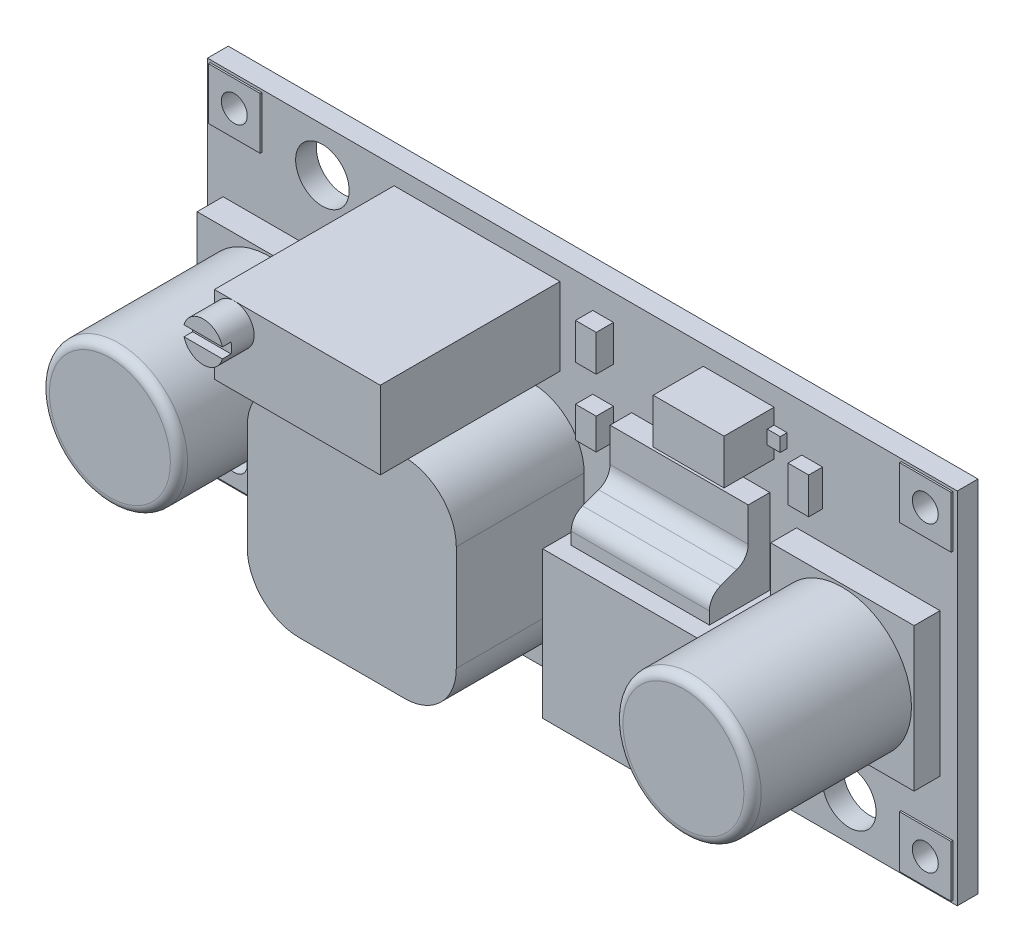
SolidWorks part; units mm, degrees
ref_plane "Přední rovina" through (0, 0, 0) normal (0, 0, 1) x (1, 0, 0)
ref_plane "Horní rovina" through (0, 0, 0) normal (0, 1, 0) x (1, 0, 0)
ref_plane "Pravá rovina" through (0, 0, 0) normal (1, 0, 0) x (0, 0, -1)
sketch "Skica1" plane through (0, 0, 0) normal (0, 0, 1) x (1, 0, 0)
  line L1 (-21.7, -10.4) -> (21.7, -10.4)
  line L2 (-21.7, -10.4) -> (-21.7, 10.4)
  line L3 (-21.7, 10.4) -> (21.7, 10.4)
  line L4 (21.7, -10.4) -> (21.7, 10.4)
  line L5 (-21.7, -10.4) -> (21.7, 10.4) construction
  line L6 (-21.7, 10.4) -> (21.7, -10.4) construction
  circle A0 centre (-15.05, 7.85) radius 1.55
  circle A1 centre (15.45, -8.05) radius 1.55
  point P0 (0, 0)
  dimension "D3" = 3.1
  dimension "D4" = 1
  dimension "D5" = 0.8
  dimension "D6" = 5.1
  dimension "D7" = 4.7
  dimension "D1" = 43.4
  dimension "D2" = 20.8
extrude "Přidat vysunutím1" add sketch "Skica1" along normal blind 1.2
sketch "Skica3" plane through (0, 0, 1.2) normal (0, 0, 1) x (1, 0, 0)
  line L0 (-21.7, -10.4) -> (21.7, -10.4) construction
  line L1 (-12, -8.6) -> (0.1, -8.6)
  line L2 (-12, -8.6) -> (-12, 3.5)
  line L3 (-12, 3.5) -> (0.1, 3.5)
  line L4 (0.1, -8.6) -> (0.1, 3.5)
  line L5 (-12, -8.6) -> (0.1, 3.5) construction
  line L6 (-12, 3.5) -> (0.1, -8.6) construction
  line L7 (-21.7, 10.4) -> (-21.7, -10.4) construction
  point P0 (-5.95, -2.55)
  dimension "D1" = 12.1
  dimension "D2" = 1.8
  dimension "D3" = 9.7
extrude "Přidat vysunutím2" add sketch "Skica3" along normal blind 7.4
fillet "Zaoblit1" radius 3 4 edges at (-12, -8.6, 4.9) (-12, 3.5, 4.9) (0.1, 3.5, 4.9) (0.1, -8.6, 4.9)
sketch "Skica4" plane through (0, 0, 1.2) normal (0, 0, 1) x (1, 0, 0)
  line L0 (21.7, 10.4) -> (-21.7, 10.4) construction
  line L1 (-1.3, 4.9) -> (-10.9, 4.9)
  line L2 (-1.3, 4.9) -> (-1.3, 9.4)
  line L3 (-1.3, 9.4) -> (-10.9, 9.4)
  line L4 (-10.9, 4.9) -> (-10.9, 9.4)
  line L5 (-1.3, 4.9) -> (-10.9, 9.4) construction
  line L6 (-1.3, 9.4) -> (-10.9, 4.9) construction
  line L7 (-21.7, 10.4) -> (-21.7, -10.4) construction
  point P0 (-6.1, 7.15)
  dimension "D1" = 4.5
  dimension "D2" = 9.6
  dimension "D3" = 1
  dimension "D4" = 10.8
extrude "Přidat vysunutím3" add sketch "Skica4" along normal blind 10.4
sketch "Skica5" plane through (0, 0, 11.6) normal (0, 0, 1) x (1, 0, 0)
  line L0 (-1.3, 9.4) -> (-10.9, 9.4) construction
  line L1 (-10.9, 9.4) -> (-10.9, 4.9) construction
  circle A0 centre (-9.75, 8.25) radius 1.15
  dimension "D1" = 2.3
extrude "Přidat vysunutím4" add sketch "Skica5" along normal blind 1.8
sketch "Skica6" plane through (0, 0, 1.2) normal (0, 0, 1) x (1, 0, 0)
  line L0 (-21.7, 10.4) -> (-21.7, -10.4) construction
  line L1 (-12.5, -4.4) -> (-20.8, -4.4)
  line L2 (-12.5, -4.4) -> (-12.5, 3.9)
  line L3 (-12.5, 3.9) -> (-20.8, 3.9)
  line L4 (-20.8, -4.4) -> (-20.8, 3.9)
  line L5 (-12.5, -4.4) -> (-20.8, 3.9) construction
  line L6 (-12.5, 3.9) -> (-20.8, -4.4) construction
  line L7 (20.7, -4.4) -> (12.4, -4.4)
  line L8 (20.7, -4.4) -> (20.7, 3.9)
  line L9 (20.7, 3.9) -> (12.4, 3.9)
  line L10 (12.4, -4.4) -> (12.4, 3.9)
  line L11 (20.7, -4.4) -> (12.4, 3.9) construction
  line L12 (20.7, 3.9) -> (12.4, -4.4) construction
  line L13 (21.7, -10.4) -> (21.7, 10.4) construction
  line L14 (21.7, 10.4) -> (-21.7, 10.4) construction
  circle A0 centre (-16.65, -0.25) radius 4
  circle A1 centre (16.55, -0.25) radius 4
  point P0 (-16.65, -0.25)
  point P5 (16.55, -0.25)
  dimension "D4" = 8
  dimension "D1" = 0.9
  dimension "D2" = 1
  dimension "D3" = 6.5
  dimension "D5" = 8.3
extrude "Přidat vysunutím5" add sketch "Skica6" along normal blind 1.5
extrude "Přidat vysunutím6" add sketch "Skica6<2>" along normal blind 10.7 contours A0 | A1 region at (-16.65, -0.25, 1.2) region at (16.55, -0.25, 1.2)
sketch "Skica6<2>" plane through (0, 0, 1.2) normal (0, 0, 1) x (1, 0, 0) same geometry as "Skica6"
fillet "Zaoblit2" radius 0.5 2 edges at (20.55, -0.25, 11.9) (-12.65, -0.25, 11.9)
sketch "Skica7" plane through (0, 0, 1.2) normal (0, 0, 1) x (1, 0, 0)
  line L0 (-21.7, -10.4) -> (21.7, -10.4) construction
  line L1 (2.2, -8.5) -> (11.5, -8.5)
  line L2 (2.2, -8.5) -> (2.2, 0)
  line L3 (2.2, 0) -> (11.5, 0)
  line L4 (11.5, -8.5) -> (11.5, 0)
  line L5 (2.2, -8.5) -> (11.5, 0) construction
  line L6 (2.2, 0) -> (11.5, -8.5) construction
  line L7 (2.2, -9.8) -> (11.5, -9.8)
  line L8 (2.2, -9.8) -> (2.2, 0)
  line L9 (2.2, 0) -> (11.5, 0)
  line L10 (11.5, -9.8) -> (11.5, 0)
  line L11 (2.2, -9.8) -> (11.5, 0) construction
  line L12 (2.2, 0) -> (11.5, -9.8) construction
  line L13 (2.85, 0) -> (10.85, 0)
  line L14 (2.85, 0) -> (2.85, 4.9)
  line L15 (2.85, 4.9) -> (10.85, 4.9)
  line L16 (10.85, 0) -> (10.85, 4.9)
  line L17 (2.85, 0) -> (10.85, 4.9) construction
  line L18 (2.85, 4.9) -> (10.85, 0) construction
  line L19 (2.85, 0) -> (10.85, 0)
  line L20 (2.85, 0) -> (2.85, 1.5)
  line L21 (2.85, 1.5) -> (10.85, 1.5)
  line L22 (10.85, 0) -> (10.85, 1.5)
  line L23 (2.85, 0) -> (10.85, 1.5) construction
  line L24 (2.85, 1.5) -> (10.85, 0) construction
  line L25 (21.7, -10.4) -> (21.7, 10.4) construction
  point P0 (6.85, -4.25)
  point P5 (6.85, -4.9)
  point P10 (6.85, 2.45)
  point P15 (6.85, 0.75)
  dimension "D1" = 8
  dimension "D2" = 9.3
  dimension "D3" = 1.3
  dimension "D4" = 8.5
  dimension "D5" = 10
  dimension "D6" = 13.4
  dimension "D7" = 1.9
  dimension "D8" = 10.2
extrude "Přidat vysunutím7" add sketch "Skica7" along normal blind 4.5 contours L1 L4 L3 L9 L2 region at (6.85, -4.25, 1.2)
extrude "Přidat vysunutím8" add sketch "Skica7<3>" along normal blind 1.4 contours L7 L10 L1 L8 region at (6.85, -9.15, 1.2)
sketch "Skica7<3>" plane through (0, 0, 1.2) normal (0, 0, 1) x (1, 0, 0) same geometry as "Skica7"
extrude "Přidat vysunutím9" add sketch "Skica7<4>" along normal blind 1.25 contours L14 L21 L16 L15 region at (6.85, 3.2, 1.2)
sketch "Skica7<4>" plane through (0, 0, 1.2) normal (0, 0, 1) x (1, 0, 0) same geometry as "Skica7"
extrude "Přidat vysunutím10" add sketch "Skica7<5>" along normal blind 3.5 contours L21 L14 L9 L16 region at (6.85, 0.75, 1.2)
sketch "Skica7<5>" plane through (0, 0, 1.2) normal (0, 0, 1) x (1, 0, 0) same geometry as "Skica7"
chamfer "Zkosení1" distance 2 angle 20 1 edges at (6.85, 1.5, 2.45) first distance on face at (6.85, 1.5, 3.575)
fillet "Zaoblit3" radius 1 1 edges at (6.85, 1.5, 4.7)
fillet "Zaoblit4" radius 1 1 edges at (6.85, 1.5, 4.45)
fillet "Zaoblit5" radius 1 1 edges at (6.85, 2.2279, 2.45)
sketch "Skica8" plane through (0, 0, 1.2) normal (0, 0, 1) x (1, 0, 0)
  line L0 (21.7, 10.4) -> (-21.7, 10.4) construction
  line L1 (7, 6.7) -> (11.1, 6.7)
  line L2 (7, 6.7) -> (7, 9.3)
  line L3 (7, 9.3) -> (11.1, 9.3)
  line L4 (11.1, 6.7) -> (11.1, 9.3)
  line L5 (7, 6.7) -> (11.1, 9.3) construction
  line L6 (7, 9.3) -> (11.1, 6.7) construction
  line L7 (6.25, 7.6) -> (11.85, 7.6)
  line L8 (6.25, 7.6) -> (6.25, 8.4)
  line L9 (6.25, 8.4) -> (11.85, 8.4)
  line L10 (11.85, 7.6) -> (11.85, 8.4)
  line L11 (6.25, 7.6) -> (11.85, 8.4) construction
  line L12 (6.25, 8.4) -> (11.85, 7.6) construction
  line L13 (21.7, -10.4) -> (21.7, 10.4) construction
  point P0 (9.05, 8)
  point P5 (9.05, 8)
  dimension "D1" = 4.1
  dimension "D2" = 2.6
  dimension "D3" = 5.6
  dimension "D4" = 0.8
  dimension "D5" = 1.1
  dimension "D6" = 10.6
extrude "Přidat vysunutím11" add sketch "Skica8" along normal blind 0.4 contours L9 L10 L7 L8
extrude "Přidat vysunutím12" add sketch "Skica8<3>" along normal blind 2.9 contours L3 L4 L1 L2
sketch "Skica8<3>" plane through (0, 0, 1.2) normal (0, 0, 1) x (1, 0, 0) same geometry as "Skica8"
sketch "Skica9" plane through (0, 0, 1.2) normal (0, 0, 1) x (1, 0, 0)
  line L0 (21.7, 10.4) -> (-21.7, 10.4) construction
  line L1 (0.6, 2.9) -> (1.8, 2.9)
  line L2 (0.6, 2.9) -> (0.6, 4.7)
  line L3 (0.6, 4.7) -> (1.8, 4.7)
  line L4 (1.8, 2.9) -> (1.8, 4.7)
  line L5 (0.6, 6.8) -> (1.8, 6.8)
  line L6 (0.6, 6.8) -> (0.6, 8.9)
  line L7 (0.6, 8.9) -> (1.8, 8.9)
  line L8 (1.8, 6.8) -> (1.8, 8.9)
  line L9 (21.7, -10.4) -> (21.7, 10.4) construction
  point P12 (1.2, 4.7)
  dimension "D1" = 1.2
  dimension "D2" = 2.1
  dimension "D3" = 1.5
  dimension "D4" = 7.5
  dimension "D5" = 19.9
  dimension "D6" = 5.7
extrude "Přidat vysunutím13" add sketch "Skica9" along normal blind 1
sketch "Skica10" plane through (0, 0, 1.2) normal (0, 0, 1) x (1, 0, 0)
  line L0 (21.7, 10.4) -> (-21.7, 10.4) construction
  line L1 (12.7, 5.6) -> (13.9, 5.6)
  line L2 (12.7, 5.6) -> (12.7, 7.7)
  line L3 (12.7, 7.7) -> (13.9, 7.7)
  line L4 (13.9, 5.6) -> (13.9, 7.7)
  line L5 (21.7, -10.4) -> (21.7, 10.4) construction
  dimension "D1" = 1.2
  dimension "D2" = 2.1
  dimension "D3" = 2.7
  dimension "D4" = 7.8
extrude "Přidat vysunutím14" add sketch "Skica10" along normal blind 0.8
sketch "Skica11" plane through (0, 0, 1.2) normal (0, 0, 1) x (1, 0, 0)
  line L0 (21.7, 10.4) -> (-21.7, 10.4) construction
  line L2 (-21.7, 10.4) -> (-21.7, -10.4) construction
  line L3 (21.7, -10.4) -> (21.7, 10.4) construction
  line L5 (21.45, -10.25) -> (18.45, -10.25)
  line L6 (21.45, -10.25) -> (21.45, -7.25)
  line L7 (21.45, -7.25) -> (18.45, -7.25)
  line L8 (18.45, -10.25) -> (18.45, -7.25)
  line L9 (21.45, -10.25) -> (18.45, -7.25) construction
  line L10 (21.45, -7.25) -> (18.45, -10.25) construction
  line L11 (21.45, 10.25) -> (18.45, 10.25)
  line L12 (21.45, 10.25) -> (21.45, 7.25)
  line L13 (21.45, 7.25) -> (18.45, 7.25)
  line L14 (18.45, 10.25) -> (18.45, 7.25)
  line L15 (21.45, 10.25) -> (18.45, 7.25) construction
  line L16 (21.45, 7.25) -> (18.45, 10.25) construction
  line L17 (-21.55, -10.25) -> (-18.55, -10.25)
  line L18 (-21.55, -10.25) -> (-21.55, -7.25)
  line L19 (-21.55, -7.25) -> (-18.55, -7.25)
  line L20 (-18.55, -10.25) -> (-18.55, -7.25)
  line L21 (-21.55, -10.25) -> (-18.55, -7.25) construction
  line L22 (-21.55, -7.25) -> (-18.55, -10.25) construction
  line L23 (-21.55, 10.25) -> (-18.55, 10.25)
  line L24 (-21.55, 10.25) -> (-21.55, 7.25)
  line L25 (-21.55, 7.25) -> (-18.55, 7.25)
  line L26 (-18.55, 10.25) -> (-18.55, 7.25)
  line L27 (-21.55, 10.25) -> (-18.55, 7.25) construction
  line L28 (-21.55, 7.25) -> (-18.55, 10.25) construction
  circle A0 centre (-20.05, 8.75) radius 0.75
  circle A1 centre (-20.05, -8.75) radius 0.75
  circle A2 centre (19.95, 8.75) radius 0.75
  circle A3 centre (19.95, -8.75) radius 0.75
  dimension "D2" = 1.5
  dimension "D3" = 0.9
  dimension "D4" = 0.9
  dimension "D5" = 1
  dimension "D1" = 17.5
  dimension "D6" = 3
extrude "Přidat vysunutím15" add sketch "Skica11" along normal blind 0.1 and the other way blind 1.3
extrude "Odebrat vysunutím1" cut sketch "Skica11<2>" against normal through all contours A1 | A0 | A3 | A2
sketch "Skica11<2>" plane through (0, 0, 1.2) normal (0, 0, 1) x (1, 0, 0) same geometry as "Skica11"
sketch "Skica12" plane through (0, 0, 13.4) normal (0, 0, 1) x (1, 0, 0)
  line L1 (-11.5794, 7.95) -> (-7.9206, 7.95)
  line L2 (-11.5794, 7.95) -> (-11.5794, 8.55)
  line L3 (-11.5794, 8.55) -> (-7.9206, 8.55)
  line L4 (-7.9206, 7.95) -> (-7.9206, 8.55)
  line L5 (-11.5794, 7.95) -> (-7.9206, 8.55) construction
  line L6 (-11.5794, 8.55) -> (-7.9206, 7.95) construction
  point P0 (-9.75, 8.25)
  dimension "D1" = 0.6
extrude "Odebrat vysunutím2" cut sketch "Skica12" against normal blind 0.5
sketch "Skica13" plane through (0, 0, 0) normal (0, 0, -1) x (-1, 0, 0)
  line L0 (6.25, 6.4) -> (6.25, 8.361) construction
  line L1 (3.1, 6.4) -> (4.6, 6.4)
  line L2 (3.1, 6.4) -> (3.1, 7.9)
  line L3 (3.1, 7.9) -> (4.6, 7.9)
  line L4 (4.6, 6.4) -> (4.6, 7.9)
  line L5 (5.5, 6.4) -> (7, 6.4)
  line L6 (5.5, 6.4) -> (5.5, 7.9)
  line L7 (5.5, 7.9) -> (7, 7.9)
  line L8 (7, 6.4) -> (7, 7.9)
  line L9 (7.9, 6.4) -> (9.4, 6.4)
  line L10 (7.9, 6.4) -> (7.9, 7.9)
  line L11 (7.9, 7.9) -> (9.4, 7.9)
  line L12 (9.4, 6.4) -> (9.4, 7.9)
  line L13 (-21.7, 10.4) -> (21.7, 10.4) construction
  line L14 (21.7, 10.4) -> (21.7, -10.4) construction
  dimension "D1" = 1.5
  dimension "D2" = 6.3
  dimension "D3" = 2.5
  dimension "D4" = 12.3
extrude "Přidat vysunutím16" add sketch "Skica13" along normal blind 1.1
